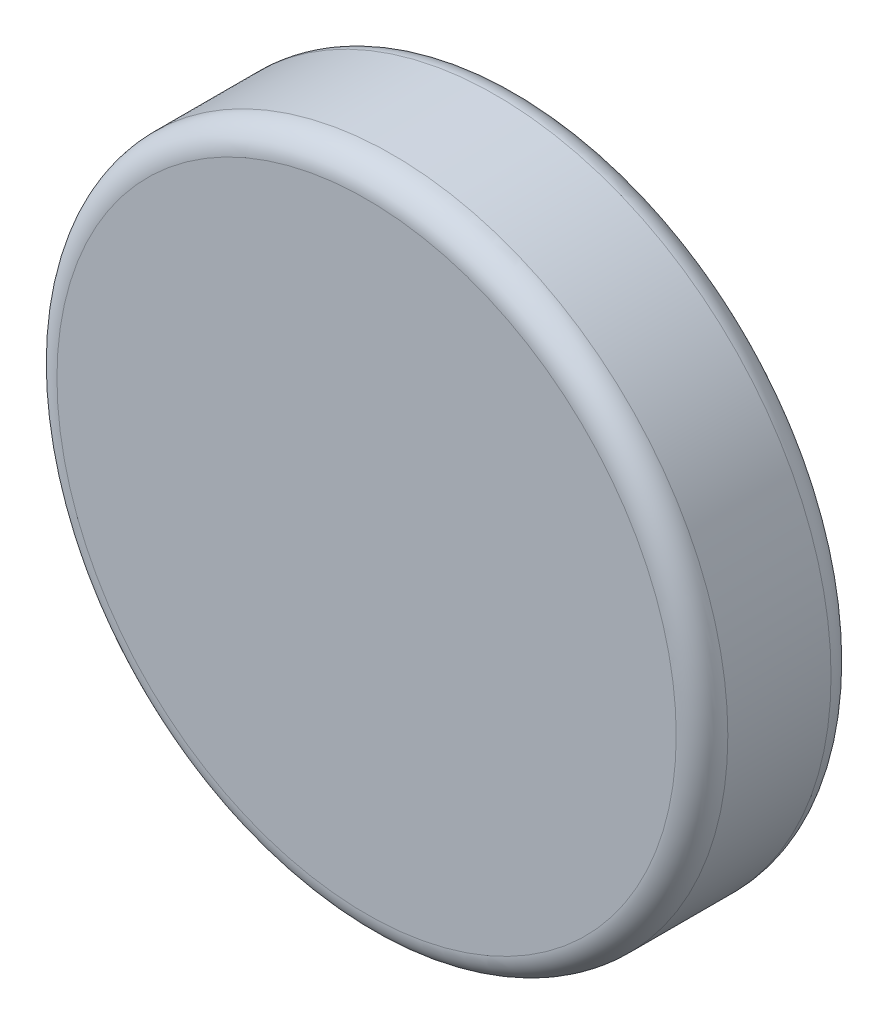
SolidWorks part; units mm, degrees
ref_plane "Спереди" through (0, 0, 0) normal (0, 0, 1) x (1, 0, 0)
ref_plane "Сверху" through (0, 0, 0) normal (0, 1, 0) x (1, 0, 0)
ref_plane "Справа" through (0, 0, 0) normal (1, 0, 0) x (0, 0, -1)
sketch "Эскиз1" plane through (0, 0, 0) normal (0, 0, 1) x (1, 0, 0)
  circle A0 centre (0, 0) radius 13
  dimension "D1" = 26
extrude "Бобышка-Вытянуть1" add sketch "Эскиз1" along normal blind 6
sketch "Эскиз2" plane through (0, 0, 0) normal (0, 0, -1) x (-1, 0, 0)
  circle A0 centre (0, 0) radius 0.725
  dimension "D1" = 1.45
extrude "Вырез-Вытянуть1" cut sketch "Эскиз2" against normal blind 4
sketch "Эскиз3" plane through (0, 0, 0) normal (0, 0, -1) x (-1, 0, 0)
  circle A0 centre (0, 0) radius 11
  circle A1 centre (0, 0) radius 2.5
  dimension "D1" = 5
  dimension "D2" = 22
extrude "Вырез-Вытянуть2" cut sketch "Эскиз3" against normal blind 4 contours A0 | A1
fillet "Скругление1" radius 1 2 edges at (13, 0, 0) (-11, 0, 0)
fillet "Скругление2" radius 1 1 edges at (13, 0, 6)
fillet "Скругление3" radius 0.2 2 edges at (-2.5, 0, 0) (-0.725, 0, 0)
fillet "Скругление4" radius 0.2 2 edges at (-11, 0, 4) (-2.5, 0, 4)
